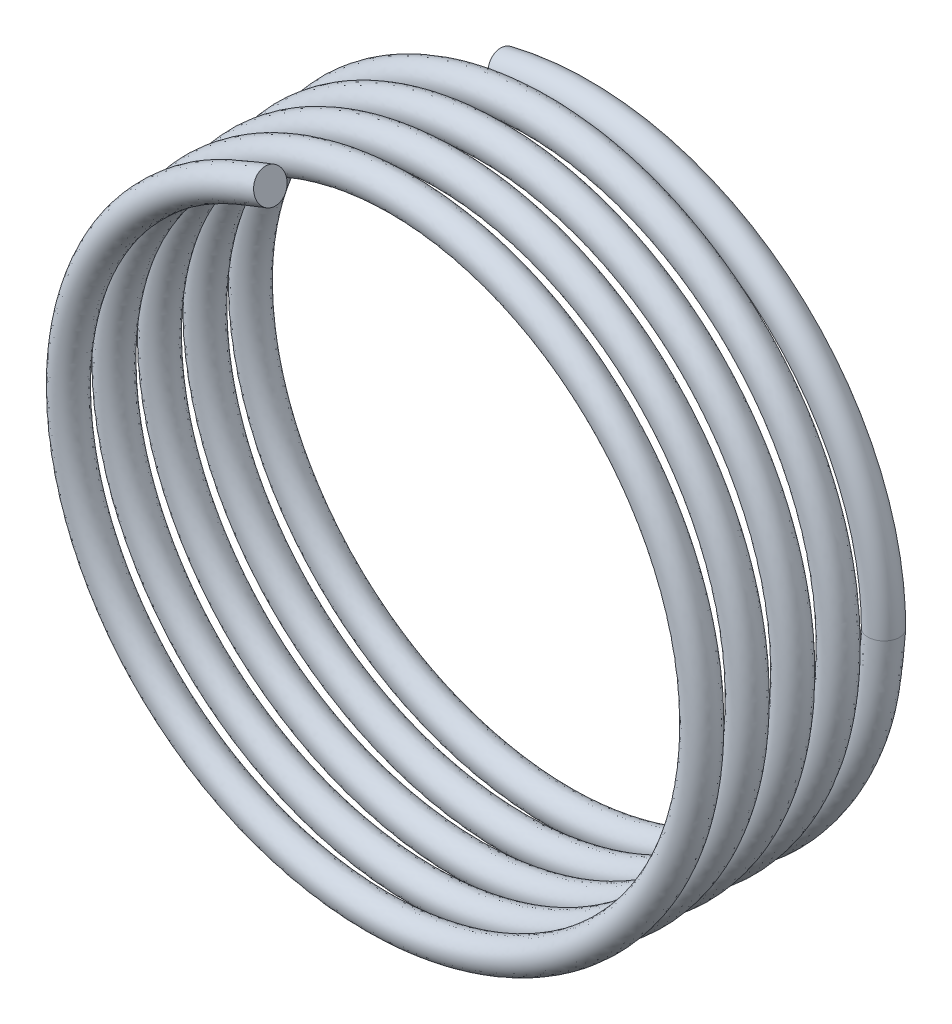
SolidWorks part; units mm, degrees
note: '?' marks a value the reader was unsure of.
material "AISI Type A2 Tool Steel"
ref_plane "FRONT" through (0, 0, 0) normal (0, 0, 1) x (1, 0, 0)
ref_plane "TOP" through (0, 0, 0) normal (0, 1, 0) x (1, 0, 0)
ref_plane "SIDE" through (0, 0, 0) normal (1, 0, 0) x (0, 0, -1)
sketch "Sketch1" plane through (0, 0, 0) normal (0, 0, 1) x (1, 0, 0)
  circle A0 centre (0, 0) radius 11.6078
  dimension "D1" = 23.2156
curve "Helix1" pitch 1.7294 height 8.128 turns 4.7
ref_plane "Plane4" through (-3.587, 11.0397, 8.128) normal (0.9508, 0.3089, 0.0237) x (-0.3098, 0.948, 0.0727)
sketch "Sketch2" plane through (-3.587, 11.0397, 8.128) normal (0.9508, 0.3089, 0.0237) x (-0.3098, 0.948, 0.0727)
  circle A0 centre (0, 0) radius 0.5969
  dimension "D1" = 1.1938
sweep "Base-Sweep" add profiles "Sketch2" path "Helix1"
sketch "Sketch3" plane through (0, 0, 0) normal (0, 0, 1) x (1, 0, 0)
  line L0 (-2.8082, 11.263) -> (0, 0) construction
  line L1 (11.6078, 0) -> (0, 0) construction
  circle A1 centre (0, 0) radius 11.6078
  arc A2 (11.6078, 0) -> (-2.8082, 11.263) centre (0, 0) ccw
  dimension "D2" = 256
  dimension "D1" = 0
sketch "Sketch4" plane through (0, 0, 0) normal (0, 0.9997, -0.0237) x (-1, 0, 0)
  circle A1 centre (-11.6078, 0) radius 0.5969
  circle A2 centre (-11.6078, 0) radius 0.5969
  dimension "D1" = 0
sweep "Boss-Sweep1" add profiles "Sketch4" path "Sketch3"
ref_plane "Plane5" through (0, 0, -0.5969) normal (0, 0, 1) x (1, 0, 0)
ref_axis "Axis1" through (0, 0, 11.8736) along (0, 0, -1)?
